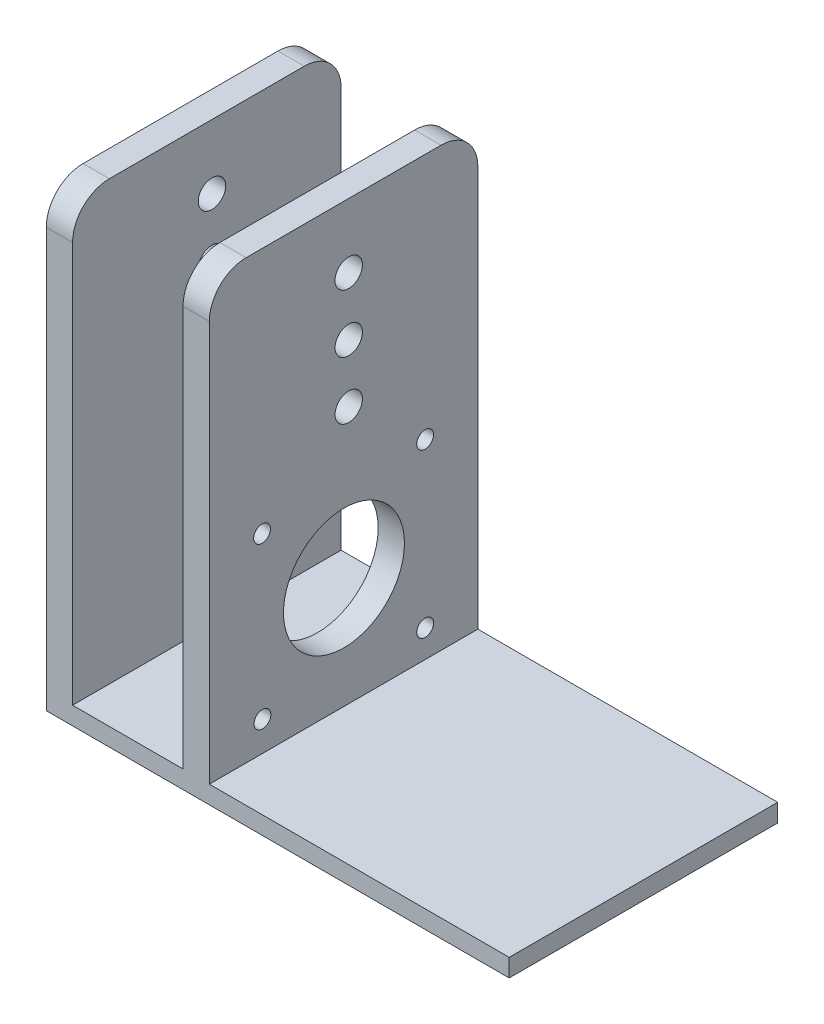
SolidWorks part; units mm, degrees
ref_plane "Front Plane" through (0, 0, 0) normal (0, 0, 1) x (1, 0, 0)
ref_plane "Top Plane" through (0, 0, 0) normal (0, 1, 0) x (1, 0, 0)
ref_plane "Right Plane" through (0, 0, 0) normal (1, 0, 0) x (0, 0, -1)
sketch "Sketch1" plane through (0, 0, 0) normal (0, 1, 0) x (1, 0, 0)
  line L1 (-44.0031, -25.5222) -> (44.0031, -25.5222)
  line L2 (-44.0031, -25.5222) -> (-44.0031, 25.5222)
  line L3 (-44.0031, 25.5222) -> (44.0031, 25.5222)
  line L4 (44.0031, -25.5222) -> (44.0031, 25.5222)
  line L5 (-44.0031, -25.5222) -> (44.0031, 25.5222) construction
  line L6 (-44.0031, 25.5222) -> (44.0031, -25.5222) construction
  point P0 (0, 0)
extrude "Boss-Extrude1" add sketch "Sketch1" along normal blind 3.4061
sketch "Sketch2" plane through (0, 3.4061, 0) normal (0, 1, 0) x (1, 0, 0)
  line L0 (-13.0031, 25.5222) -> (-18.0031, 25.5222)
  line L1 (44.0031, 25.5222) -> (-44.0031, 25.5222) construction
  line L2 (-18.0031, 25.5222) -> (-18.0031, -25.5222)
  line L3 (-44.0031, -25.5222) -> (44.0031, -25.5222) construction
  line L4 (-18.0031, -25.5222) -> (-13.0031, -25.5222)
  line L5 (-13.0031, -25.5222) -> (-13.0031, 25.5222)
  line L6 (-44.0031, 25.5222) -> (-44.0031, -25.5222) construction
  dimension "D1" = 5
  dimension "D2" = 26
extrude "Boss-Extrude3" add sketch "Sketch2" along normal blind 83.1809
sketch "Sketch8" plane through (-13.0031, 0, 0) normal (1, 0, 0) x (0, 0, -1)
  circle A0 centre (0.0714, 24.5561) radius 11.5
extrude "Cut-Extrude3" cut sketch "Sketch8" against normal through all
sketch "Sketch9" plane through (-13.0031, 0, 0) normal (1, 0, 0) x (0, 0, -1)
  circle A0 centre (-15.4286, 9.0561) radius 1.6
  circle A1 centre (-15.5, 39.65) radius 1.6
  circle A2 centre (15.5, 39.65) radius 1.6
  circle A3 centre (15.5, 8.65) radius 1.6
extrude "Cut-Extrude4" cut sketch "Sketch9" against normal through all
sketch "Sketch17" plane through (-44.0031, -0.0607, 0) normal (-1, 0, 0) x (0, 0, 1)
  line L9 (-25.5222, 0.0607) -> (25.5222, 0.0607)
  line L10 (-25.5222, 0.0607) -> (-25.5222, 86.6476)
  line L11 (-25.5222, 86.6476) -> (25.5222, 86.6476)
  line L12 (25.5222, 0.0607) -> (25.5222, 86.6476)
extrude "Boss-Extrude4" add sketch "Sketch17" against normal blind 5
sketch "Sketch20" plane through (-13.0031, 0, 0) normal (1, 0, 0) x (0, 0, -1)
  line L0 (0.9742, 86.587) -> (0.9742, 46.6273) construction
  line L1 (-25.5222, 86.587) -> (25.5222, 86.587) construction
  circle A0 centre (0.9742, 74.3728) radius 2.605
  circle A1 centre (0.9742, 63.2987) radius 2.605
  dimension "5.2" = 5.21
  dimension "D2" = 5.21
extrude "Cut-Extrude6" cut sketch "Sketch20" against normal through all
ref_plane "Plane1" through (-39.0031, 86.587, 25.5222) normal (-1, 0, 0) x (0, 0, 1)
fillet "Fillet2" radius 7 1 edges at (-15.5031, 86.587, 25.5222)
fillet "Fillet4" radius 7 1 edges at (-41.5031, 86.587, 25.5222)
fillet "Fillet5" radius 7 1 edges at (-15.5031, 86.587, -25.5222)
fillet "Fillet6" radius 7 1 edges at (-41.5031, 86.587, -25.5222)
sketch "Sketch21" plane through (-13.0031, 0, 0) normal (1, 0, 0) x (0, 0, -1)
  line L0 (0.9742, 82.8594) -> (0.9742, 45.1185) construction
  line L1 (0.9742, 74.3728) -> (-7.5105, 74.3728) construction
  line L2 (0.9742, 63.2987) -> (-7.5105, 63.2987) construction
  circle A0 centre (0.9742, 52.2987) radius 2.6
  dimension "D1" = 5.2
  dimension "D2" = 11
extrude "Cut-Extrude7" cut sketch "Sketch21" against normal through all
sketch "Sketch23" plane through (-13.0031, 0, 0) normal (1, 0, 0) x (0, 0, -1)
  line L0 (0.9742, 74.3728) -> (-9.1708, 74.3728) construction
  line L1 (0.9742, 63.2987) -> (-9.1708, 63.2987) construction
  line L2 (0.9742, 79.6741) -> (0.9742, 46.4598) construction
  line L3 (0.9742, 52.2987) -> (-9.6651, 52.2987) construction
  dimension "D1" = 11.0741
sketch "Sketch26" plane through (0, 3.4061, 0) normal (0, 1, 0) x (1, 0, 0)
